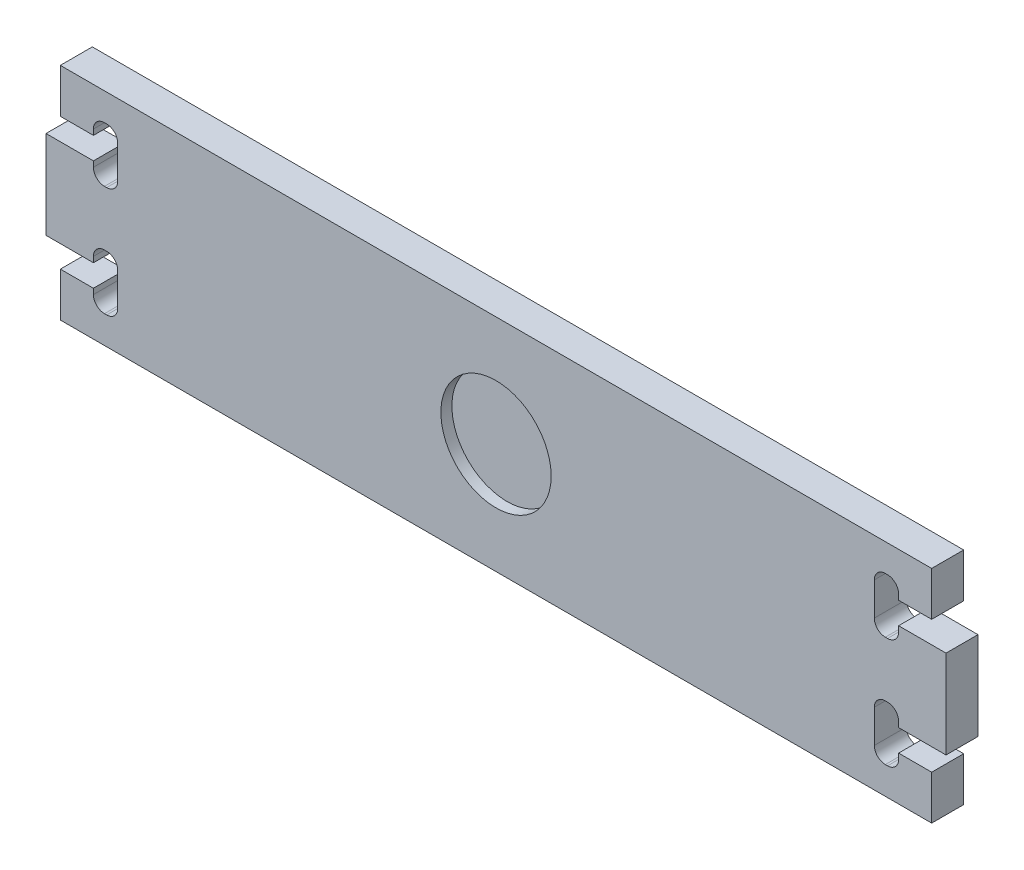
SolidWorks part; units mm, degrees
ref_plane "Front Plane" through (0, 0, 0) normal (0, 0, 1) x (1, 0, 0)
ref_plane "Top Plane" through (0, 0, 0) normal (0, 1, 0) x (1, 0, 0)
ref_plane "Right Plane" through (0, 0, 0) normal (1, 0, 0) x (0, 0, -1)
sketch "Sketch1" plane through (0, 0, 0) normal (0, 0, 1) x (1, 0, 0)
  line L0 (-39.5, 0) -> (39.5, 0) construction
  line L1 (-39.5, 10) -> (39.5, 10)
  line L2 (-39.5, 10) -> (-39.5, -10)
  line L3 (-39.5, -10) -> (39.5, -10)
  line L4 (39.5, 10) -> (39.5, -10)
  line L5 (-39.5, 10) -> (39.5, -10) construction
  line L6 (-39.5, -10) -> (39.5, 10) construction
  line L7 (0, 10) -> (0, -10) construction
  line L9 (-40.8, -4) -> (-39.5, -4)
  line L10 (-40.8, -4) -> (-40.8, 4)
  line L11 (-40.8, 4) -> (-39.5, 4)
  line L12 (-39.5, -4) -> (-39.5, 4)
  line L13 (-40.8, -4) -> (-39.5, 4) construction
  line L14 (-40.8, 4) -> (-39.5, -4) construction
  line L16 (40.8, 4) -> (39.5, 4)
  line L17 (40.8, -4) -> (40.8, 4)
  line L18 (40.8, -4) -> (39.5, -4)
  line L19 (-39.5, 5) -> (39.5, 5) construction
  line L20 (-35.4, 7.5) -> (-35.4, 2.5) construction
  line L21 (-36.5, 4) -> (-39.5, 4)
  line L22 (-36.5, 4) -> (-36.5, 6)
  line L23 (-36.5, 6) -> (-39.5, 6)
  line L24 (-39.5, 4) -> (-39.5, 6)
  line L25 (-36.5, 4) -> (-39.5, 6) construction
  line L26 (-36.5, 6) -> (-39.5, 4) construction
  line L27 (-34.3, 7.5) -> (-36.5, 7.5)
  line L28 (-34.3, 7.5) -> (-34.3, 2.5)
  line L29 (-34.3, 2.5) -> (-36.5, 2.5)
  line L30 (-36.5, 7.5) -> (-36.5, 2.5)
  line L31 (-34.3, 7.5) -> (-36.5, 2.5) construction
  line L32 (-34.3, 2.5) -> (-36.5, 7.5) construction
  line L33 (-34.3, -7.5) -> (-36.5, -7.5)
  line L34 (-34.3, -7.5) -> (-34.3, -2.5)
  line L35 (-34.3, -2.5) -> (-36.5, -2.5)
  line L36 (-36.5, -7.5) -> (-36.5, -2.5)
  line L37 (-36.5, -4) -> (-39.5, -4)
  line L38 (-36.5, -6) -> (-39.5, -6)
  line L39 (36.5, 4) -> (39.5, 4)
  line L40 (36.5, 6) -> (39.5, 6)
  line L41 (36.5, 7.5) -> (36.5, 2.5)
  line L42 (34.3, 7.5) -> (36.5, 7.5)
  line L43 (34.3, 7.5) -> (34.3, 2.5)
  line L44 (34.3, 2.5) -> (36.5, 2.5)
  line L45 (34.3, -2.5) -> (36.5, -2.5)
  line L46 (34.3, -7.5) -> (34.3, -2.5)
  line L47 (34.3, -7.5) -> (36.5, -7.5)
  line L48 (36.5, -7.5) -> (36.5, -2.5)
  line L49 (36.5, -6) -> (39.5, -6)
  line L50 (36.5, -4) -> (39.5, -4)
  point P0 (0, 0)
  point P10 (-40.15, 0)
  point P15 (-38, 5)
  point P35 (-35.4, 5)
  dimension "D1" = 79
  dimension "D2" = 20
  dimension "D4" = 1.3
  dimension "D7" = 5
  dimension "D8" = 2
  dimension "D9" = 3
  dimension "D10" = 2.2
  dimension "D11" = 5
extrude "Base shape" add sketch "Sketch1" along normal blind 2.9 contours L4 L1 L2 L3 | L9 L2 L11 L10 | L16 L4 L18 L17 region at (0, 0, 0) region at (-40.15, 0, 0) region at (40.15, 0, 0)
sketch "Sketch2" plane through (0, 0, 2.9) normal (0, 0, 1) x (1, 0, 0)
  circle A0 centre (0, 0) radius 5
  dimension "D1" = 10
extrude "Forward cut (temp)" cut sketch "Sketch2" against normal blind 1
fillet "Fillet1" radius 1 16 edges at (36.5, -7.5, 1.45) (36.5, 2.5, 1.45) (34.3, 2.5, 1.45) (34.3, -7.5, 1.45) (36.5, -2.5, 1.45) (36.5, 7.5, 1.45) (34.3, -2.5, 1.45) (34.3, 7.5, 1.45) (-36.5, -2.5, 1.45) (-34.3, -2.5, 1.45) (-34.3, -7.5, 1.45) (-36.5, -7.5, 1.45) (-36.5, 2.5, 1.45) (-34.3, 2.5, 1.45) (-34.3, 7.5, 1.45) (-36.5, 7.5, 1.45)
sketch "Sketch3" plane through (-40.8, 0, 0) normal (-1, 0, 0) x (0, 0, 1)
  line L0 (0, 6) -> (2.9, 4) construction
  line L1 (0, 6) -> (2.9, 6)
  line L2 (0, 6) -> (0, 4)
  line L3 (0, 4) -> (2.9, 4)
  line L4 (2.9, 6) -> (2.9, 4)
  line L5 (0, -4) -> (2.9, -6) construction
  line L6 (0, -4) -> (2.9, -4)
  line L7 (0, -4) -> (0, -6)
  line L8 (0, -6) -> (2.9, -6)
  line L9 (2.9, -4) -> (2.9, -6)
  point P6 (1.45, 5)
  point P13 (1.45, -5)
ref_axis "Tap axis top" through (-53.7846, 5, 1.45) along (1, 0, 0)
ref_axis "Tap axis bottom" through (-54.2844, -5, 1.45) along (1, 0, 0)
